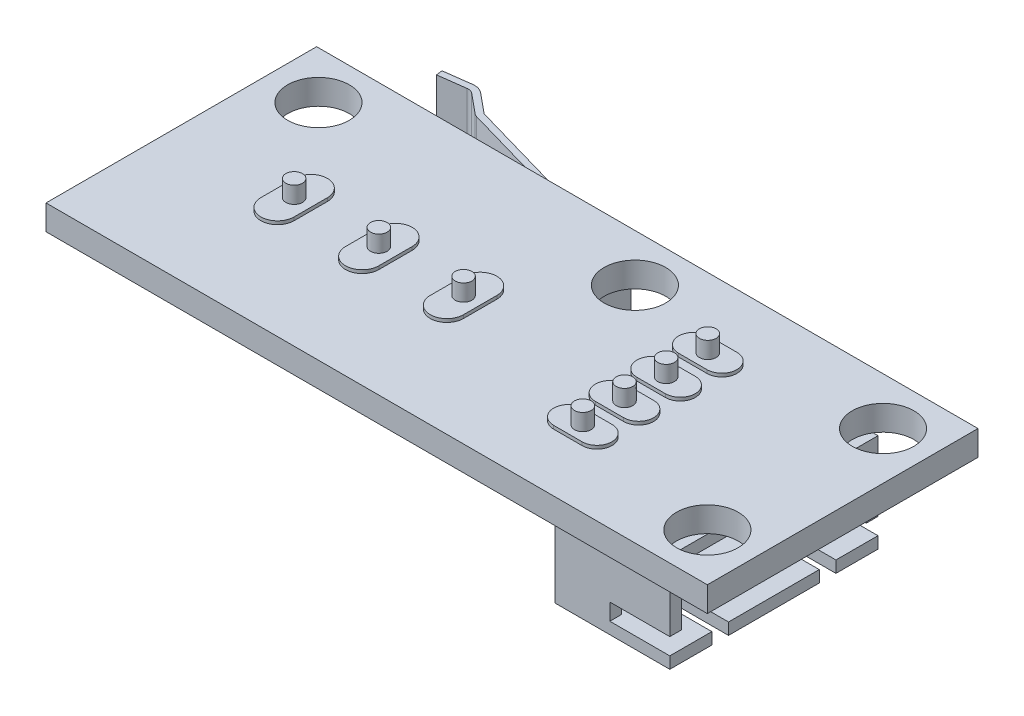
SolidWorks part; units mm, degrees
material "ABS"
ref_plane "Front Plane" through (0, 0, 0) normal (0, 0, 1) x (1, 0, 0)
ref_plane "Top Plane" through (0, 0, 0) normal (0, 1, 0) x (1, 0, 0)
ref_plane "Right Plane" through (0, 0, 0) normal (1, 0, 0) x (0, 0, -1)
sketch "Sketch1" plane through (0, 0, 0) normal (0, 1, 0) x (1, 0, 0)
  line L0 (-19.855, 0) -> (19.855, 0) construction
  line L1 (-19.855, -8.125) -> (19.855, -8.125)
  line L2 (-19.855, -8.125) -> (-19.855, 8.125)
  line L3 (-19.855, 8.125) -> (19.855, 8.125)
  line L4 (19.855, -8.125) -> (19.855, 8.125)
  line L5 (-19.855, -8.125) -> (19.855, 8.125) construction
  line L6 (-19.855, 8.125) -> (19.855, -8.125) construction
  line L7 (-19.855, 5.275) -> (19.855, 5.275) construction
  line L8 (17.005, 8.125) -> (17.005, -8.125) construction
  line L9 (0, 8.125) -> (0, -8.125) construction
  circle A0 centre (17.005, 5.275) radius 1.85
  circle A2 centre (17.005, -5.275) radius 1.85
  circle A3 centre (2.105, 5.275) radius 1.85
  circle A4 centre (-16.895, 5.275) radius 1.85
  point P0 (0, 0)
  point P16 (18.855, -5.275)
  point P17 (17.005, 3.425)
  point P24 (17.005, -3.425)
  point P25 (17.005, 7.125)
  point P26 (15.155, 5.275)
  point P27 (-15.045, 5.275)
  dimension "D3" = 3.7
  dimension "D6" = 19
  dimension "D1" = 16.25
  dimension "D2" = 39.71
  dimension "D4" = 1
  dimension "D5" = 1
  dimension "D7" = 30.2
extrude "Boss-Extrude1" add sketch "Sketch1" along normal blind 1.5
sketch "Sketch2" plane through (0, 0, 0) normal (0, -1, 0) x (1, 0, 0)
  line L0 (19.855, 0) -> (-19.855, 0) construction
  line L1 (19.855, 8.125) -> (19.855, -8.125) construction
  line L2 (-19.855, -8.125) -> (-19.855, 8.125) construction
  line L4 (15.725, -6.25) -> (8.825, -6.25)
  line L5 (15.725, -6.25) -> (15.725, 6.25)
  line L6 (15.725, 6.25) -> (8.825, 6.25)
  line L7 (8.825, -6.25) -> (8.825, 6.25)
  line L8 (15.725, -6.25) -> (8.825, 6.25) construction
  line L9 (15.725, 6.25) -> (8.825, -6.25) construction
  point P6 (12.275, 0)
  dimension "D1" = 12.5
  dimension "D2" = 6.9
  dimension "D3" = 4.13
extrude "Boss-Extrude2" add sketch "Sketch2" along normal blind 5.9
sketch "Sketch3" plane through (15.725, 0, 0) normal (1, 0, 0) x (0, 0, -1)
  line L6 (-5.55, -5.2) -> (-6.25, -5.2)
  line L7 (-6.25, -5.9) -> (-6.25, 0) construction
  line L8 (5.55, -5.2) -> (6.25, -5.2)
  line L9 (6.25, -5.9) -> (6.25, 0) construction
  line L10 (-6.25, -4.2) -> (-5.55, -4.2)
  line L11 (5.55, -4.2) -> (6.25, -4.2)
  line L12 (5.55, -0.7) -> (3.9393, -0.7)
  line L13 (3.9393, -0.7) -> (-3.9393, -0.7)
  line L14 (-3.9393, -0.7) -> (-5.55, -0.7)
  line L15 (-5.55, -0.7) -> (-5.55, -5.2)
  line L16 (-5.55, -5.2) -> (5.55, -5.2)
  line L17 (5.55, -5.2) -> (5.55, -0.7)
  line L18 (5.55, -0.7) -> (3.9393, -0.7)
  line L19 (3.9393, -0.7) -> (-3.9393, -0.7)
  line L20 (-3.9393, -0.7) -> (-5.55, -0.7)
  line L21 (-5.55, -0.7) -> (-5.55, -5.2)
  line L22 (-5.55, -5.2) -> (5.55, -5.2)
  line L23 (5.55, -5.2) -> (5.55, -0.7)
  line L24 (-3.725, -5.2) -> (-3.725, -5.9)
  line L25 (6.25, -5.9) -> (-6.25, -5.9) construction
  line L26 (-2.725, -5.2) -> (-2.725, -5.9)
  line L27 (0, 0) -> (0, -5.9) construction
  line L28 (3.725, -5.2) -> (3.725, -5.9)
  line L29 (2.725, -5.2) -> (2.725, -5.9)
  line M10 (-6.25, 0) -> (-6.25, -5.9)
  line M11 (-6.25, -5.9) -> (6.25, -5.9)
  line M12 (6.25, -5.9) -> (6.25, 0)
  dimension "D2" = 1
  dimension "D3" = 1
  dimension "D4" = 5.45
  dimension "D1" = 0.7
extrude "Cut-Extrude1" cut sketch "Sketch3" against normal blind 5 contours L27 L19 L20 L21 L22 | L19 L27 L22 L23 L18 region at (15.725, -2.95, -2.775) region at (15.725, -2.95, 2.775)
extrude "Cut-Extrude2" cut sketch "Sketch3<3>" against normal blind 3.6 contours L21 L10 L6 M10 | L26 L22 L24 M11 | L22 L29 L28 M11 | L23 L8 L11 M12 region at (15.725, -4.7, 5.9) region at (15.725, -5.55, 3.225) region at (15.725, -5.55, -3.225) region at (15.725, -4.7, -5.9)
sketch "Sketch3<3>" plane through (15.725, 0, 0) normal (1, 0, 0) x (0, 0, -1) same geometry as "Sketch3"
sketch "Sketch4" plane through (0, 0, 0) normal (0, -1, 0) x (1, 0, 0)
  line L0 (-7.395, 8.125) -> (-7.395, -8.125) construction
  line L1 (-19.855, 8.125) -> (19.855, 8.125) construction
  line L2 (19.855, -8.125) -> (-19.855, -8.125) construction
  line L4 (-13.825, -1.575) -> (-0.965, -1.575)
  line L5 (-13.825, -1.575) -> (-13.825, -8.125)
  line L6 (-13.825, -8.125) -> (-0.965, -8.125)
  line L7 (-0.965, -1.575) -> (-0.965, -8.125)
  line L8 (-13.825, -1.575) -> (-0.965, -8.125) construction
  line L9 (-13.825, -8.125) -> (-0.965, -1.575) construction
  line L10 (-2.725, -1.575) -> (-2.725, 0.875)
  line L11 (-12.895, -1.575) -> (-12.065, -1.575)
  line L12 (-12.895, -1.575) -> (-12.895, 0.875)
  line L13 (-12.895, 0.875) -> (-12.065, 0.875)
  line L14 (-12.065, -1.575) -> (-12.065, 0.875)
  line L15 (-1.895, 0.875) -> (-2.725, 0.875)
  line L16 (-1.895, -1.575) -> (-1.895, 0.875)
  line L17 (-1.895, -1.575) -> (-2.725, -1.575)
  line L19 (-7.81, 0.875) -> (-6.98, 0.875)
  line L20 (-7.81, 0.875) -> (-7.81, -1.575)
  line L21 (-7.81, -1.575) -> (-6.98, -1.575)
  line L22 (-6.98, 0.875) -> (-6.98, -1.575)
  point P6 (-7.395, -4.85)
  point P11 (2.105, -5.275)
  point P12 (-16.895, -5.275)
  line M11 (-19.855, -8.125) -> (19.855, -8.125)
  dimension "D1" = 12.86
  dimension "D2" = 6.55
  dimension "D3" = 9
  dimension "D4" = 11
  dimension "D5" = 0.83
  dimension "D6" = 1.76
extrude "Boss-Extrude3" add sketch "Sketch4" along normal blind 5.75 contours L7 L4 L5 M11 region at (-7.395, 0, -4.85)
sketch "Sketch5" plane through (0, 0, -8.125) normal (0, 0, -1) x (-1, 0, 0)
  line L0 (13.825, 0) -> (0.965, 0)
split line "Split Line1"
sketch "Sketch6" plane through (0, -5.75, 0) normal (0, -1, 0) x (1, 0, 0)
  line L0 (-13.825, -4.625) -> (-9.145, -4.625)
  line L1 (-13.825, -1.575) -> (-13.825, -8.125) construction
  line L2 (-9.145, -4.625) -> (-9.145, -2.125)
  line L3 (-9.145, -2.125) -> (-5.645, -2.125)
  line L4 (-0.965, -4.625) -> (-5.645, -4.625)
  line L5 (-5.645, -4.625) -> (-5.645, -2.125)
  line L7 (-7.395, -1.575) -> (-7.395, -8.125) construction
  line L8 (-13.825, -1.575) -> (-0.965, -1.575) construction
  line L9 (-13.825, -8.125) -> (-0.965, -8.125) construction
  circle A0 centre (-10.595, -2.975) radius 1.075
  circle A1 centre (-4.195, -2.975) radius 1.075
  point P19 (-7.395, -2.125)
  dimension "D4" = 2.15
  dimension "D5" = 6.4
  dimension "D6" = 5.15
  dimension "D1" = 3.5
  dimension "D2" = 2.5
  dimension "D3" = 6
extrude "Cut-Extrude3" cut sketch "Sketch6" against normal up to surface (5.75 mm away) contours A0 | A1 up to face at (-3.6975, 0, -2.425)
sketch "Sketch7" plane through (-13.825, 0, 0) normal (-1, 0, 0) x (0, 0, 1)
  line L0 (-4.625, -5.75) -> (-4.625, 0)
  line L1 (-1.575, 0) -> (-8.125, 0) construction
sketch "Sketch8" plane through (-0.965, 0, 0) normal (1, 0, 0) x (0, 0, -1)
  line L0 (4.625, -5.75) -> (4.625, 0)
  line L1 (1.575, 0) -> (8.125, 0) construction
split line "Split Line3"
split line "Split Line4"
sketch "Sketch6<5>" plane through (0, -5.75, 0) normal (0, -1, 0) x (1, 0, 0) same geometry as "Sketch6"
split line "Split Line5"
extrude "Boss-Extrude4" add sketch "Sketch4<3>" along normal blind 3.25 contours L4 L14 L13 L12 | L22 L19 L20 L4 | L4 L16 L15 L10 region at (-12.48, 0, -0.35) region at (-7.395, 0, -0.35) region at (-2.31, 0, -0.35)
sketch "Sketch4<3>" plane through (0, 0, 0) normal (0, -1, 0) x (1, 0, 0) same geometry as "Sketch4"
sketch "Sketch9" plane through (-12.895, 0, 0) normal (-1, 0, 0) x (0, 0, 1)
  line L0 (0.875, -3.25) -> (0.875, 0) construction
  line L1 (-1.575, 0) -> (0.325, 0)
  line L2 (-1.575, 0) -> (-1.575, -2.7)
  line L3 (-1.575, -2.7) -> (0.225, -2.7)
  line L4 (0.325, 0) -> (0.325, -2.6)
  line L5 (-1.575, -3.25) -> (0.875, -3.25) construction
  line L6 (0.875, -2.6) -> (0.875, -3.25)
  line L7 (0.875, -3.25) -> (0.225, -3.25)
  arc A0 (0.325, -2.6) -> (0.225, -2.7) centre (0.225, -2.6) cw
  arc A1 (0.875, -2.6) -> (0.225, -3.25) centre (0.225, -2.6) cw
  dimension "D3" = 0.1
  dimension "D1" = 0.55
  dimension "D2" = 0.55
  dimension "D4" = 0.55
extrude "Cut-Extrude4" cut sketch "Sketch9" against normal up to surface (11 mm away) up to face at (-1.895, -1.625, -0.35)
ref_plane "Plane1" through (0, -2.875, 0) normal (0, -1, 0) x (-1, 0, 0)
sketch "Sketch10" plane through (0, -2.875, 0) normal (0, -1, 0) x (-1, 0, 0)
  line L0 (1.965, 8.125) -> (1.965, 8.225)
  line L1 (13.825, 8.125) -> (0.965, 8.125) construction
  line L2 (1.965, 8.225) -> (13.7249, 11.5963)
  line L3 (13.9053, 11.6912) -> (15.0874, 12.6663)
  line L4 (15.471, 12.7763) -> (17.0933, 12.562)
  line L5 (13.825, 4.625) -> (13.825, 8.125) construction
  line L6 (13.825, 11.625) -> (17.0933, 12.562) construction
  line L7 (15.4592, 12.0935) -> (15.2552, 12.8048) construction
  line L8 (0.965, 4.625) -> (0.965, 8.125) construction
  line L9 (1.585, 8.125) -> (1.585, 8.5114)
  line L10 (1.585, 8.5114) -> (13.6202, 11.9616)
  line L11 (13.6635, 11.9844) -> (14.8455, 12.9595)
  line L12 (15.5208, 13.153) -> (17.1431, 12.9387)
  line L13 (17.0933, 12.562) -> (17.1431, 12.9387)
  line L14 (1.585, 8.125) -> (1.965, 8.125)
  line L15 (13.6635, 11.9844) -> (14.8455, 12.9595) construction
  line L16 (1.585, 8.5114) -> (13.6202, 11.9616) construction
  arc A0 (15.471, 12.7763) -> (15.0874, 12.6663) centre (15.4055, 12.2806) ccw
  arc A1 (13.9053, 11.6912) -> (13.7249, 11.5963) centre (13.5871, 12.077) cw
  arc A2 (15.5208, 13.153) -> (14.8455, 12.9595) centre (15.4055, 12.2806) ccw
  arc A3 (13.6635, 11.9844) -> (13.6202, 11.9616) centre (13.5871, 12.077) cw
  dimension "D6" = 0.5
  dimension "D1" = 0.1
  dimension "D2" = 3.5
  dimension "D3" = 3.4
  dimension "D4" = 1
  dimension "D5" = 0.74
  dimension "D7" = 0.38
extrude "Boss-Extrude5" add sketch "Sketch10" along normal mid plane 4.14
sketch "Sketch11" plane through (0, 1.5, 0) normal (0, 1, 0) x (1, 0, 0)
  line L0 (-12.48, -0.875) -> (-12.48, -0.325) construction
  line L1 (-12.895, -0.875) -> (-12.065, -0.875) construction
  line L2 (-12.065, -0.325) -> (-12.895, -0.325) construction
  line L3 (-7.395, -0.325) -> (-7.395, -0.875) construction
  line L4 (-6.98, -0.325) -> (-7.81, -0.325) construction
  line L5 (-7.81, -0.875) -> (-6.98, -0.875) construction
  line L6 (-2.31, -0.325) -> (-2.31, -0.875) construction
  line L7 (-1.895, -0.325) -> (-2.725, -0.325) construction
  line L8 (-1.895, -0.875) -> (-2.725, -0.875) construction
  line L9 (-12.48, -1.6) -> (-12.48, 0.4) construction
  line L10 (-13.48, -1.6) -> (-13.48, 0.4)
  line L11 (-11.48, -1.6) -> (-11.48, 0.4)
  line L12 (-7.395, -1.6) -> (-7.395, 0.4) construction
  line L13 (-8.395, -1.6) -> (-8.395, 0.4)
  line L14 (-6.395, -1.6) -> (-6.395, 0.4)
  line L15 (-2.31, -1.6) -> (-2.31, 0.4) construction
  line L16 (-3.31, -1.6) -> (-3.31, 0.4)
  line L17 (-1.31, -1.6) -> (-1.31, 0.4)
  line L18 (8.825, 0) -> (15.725, 0) construction
  line L19 (8.825, -6.25) -> (8.825, 6.25) construction
  line L20 (15.725, 3.9393) -> (15.725, -3.9393) construction
  line L21 (8.005, 3.75) -> (8.005, 0) construction
  line L22 (7.155, 3.75) -> (8.855, 3.75) construction
  line L23 (7.155, 4.65) -> (8.855, 4.65)
  line L24 (7.155, 2.85) -> (8.855, 2.85)
  line L25 (7.155, 1.25) -> (8.855, 1.25) construction
  line L26 (7.155, 2.15) -> (8.855, 2.15)
  line L27 (7.155, 0.35) -> (8.855, 0.35)
  line L28 (7.155, -1.25) -> (8.855, -1.25) construction
  line L29 (7.155, -0.35) -> (8.855, -0.35)
  line L30 (7.155, -2.15) -> (8.855, -2.15)
  line L31 (7.155, -3.75) -> (8.855, -3.75) construction
  line L32 (7.155, -2.85) -> (8.855, -2.85)
  line L33 (7.155, -4.65) -> (8.855, -4.65)
  circle A0 centre (-12.48, -0.6) radius 0.5
  circle A1 centre (-7.395, -0.6) radius 0.5
  circle A2 centre (-2.31, -0.6) radius 0.5
  arc A3 (-13.48, -1.6) -> (-11.48, -1.6) centre (-12.48, -1.6) ccw
  arc A4 (-11.48, 0.4) -> (-13.48, 0.4) centre (-12.48, 0.4) ccw
  arc A5 (-8.395, -1.6) -> (-6.395, -1.6) centre (-7.395, -1.6) ccw
  arc A6 (-6.395, 0.4) -> (-8.395, 0.4) centre (-7.395, 0.4) ccw
  arc A7 (-3.31, -1.6) -> (-1.31, -1.6) centre (-2.31, -1.6) ccw
  arc A8 (-1.31, 0.4) -> (-3.31, 0.4) centre (-2.31, 0.4) ccw
  circle A9 centre (8.005, 3.75) radius 0.5
  circle A10 centre (8.005, 1.25) radius 0.5
  circle A11 centre (8.005, -1.25) radius 0.5
  circle A12 centre (8.005, -3.75) radius 0.5
  arc A13 (7.155, 4.65) -> (7.155, 2.85) centre (7.155, 3.75) ccw
  arc A14 (8.855, 2.85) -> (8.855, 4.65) centre (8.855, 3.75) ccw
  arc A15 (7.155, 2.15) -> (7.155, 0.35) centre (7.155, 1.25) ccw
  arc A16 (8.855, 0.35) -> (8.855, 2.15) centre (8.855, 1.25) ccw
  arc A17 (7.155, -0.35) -> (7.155, -2.15) centre (7.155, -1.25) ccw
  arc A18 (8.855, -2.15) -> (8.855, -0.35) centre (8.855, -1.25) ccw
  arc A19 (7.155, -2.85) -> (7.155, -4.65) centre (7.155, -3.75) ccw
  arc A20 (8.855, -4.65) -> (8.855, -2.85) centre (8.855, -3.75) ccw
  circle A21 centre (-16.895, 5.275) radius 1.85 construction
  point P26 (-12.48, -0.6)
  point P31 (-12.48, 1.4)
  point P32 (-12.48, -2.6)
  point P37 (-7.395, -0.6)
  point P44 (-2.31, -0.6)
  point P64 (8.005, 3.75)
  point P69 (9.755, 3.75)
  point P70 (6.255, 3.75)
  point P74 (8.005, 1.25)
  point P81 (8.005, -1.25)
  point P88 (8.005, -3.75)
  dimension "D1" = 1
  dimension "D5" = 1
  dimension "D6" = 2.5
  dimension "D7" = 1.25
  dimension "D8" = 24.9
  dimension "D12" = 10.17
  dimension "D2" = 2
  dimension "D3" = 4
  dimension "D9" = 3.5
  dimension "D10" = 1.8
  dimension "D4" = 3
  dimension "D11" = 4
extrude "Boss-Extrude6" add sketch "Sketch11" along normal blind 1.2 contours A0 | A1 | A2 | A9 | A10 | A11 | A12 region at (-12.48, 1.5, 0.6) region at (-7.395, 1.5, 0.6) region at (-2.31, 1.5, 0.6) region at (8.005, 1.5, -3.75) region at (8.005, 1.5, -1.25) region at (8.005, 1.5, 1.25) region at (8.005, 1.5, 3.75)
extrude "Boss-Extrude7" add sketch "Sketch11<3>" along normal blind 0.2
sketch "Sketch11<3>" plane through (0, 1.5, 0) normal (0, 1, 0) x (1, 0, 0) same geometry as "Sketch11"
